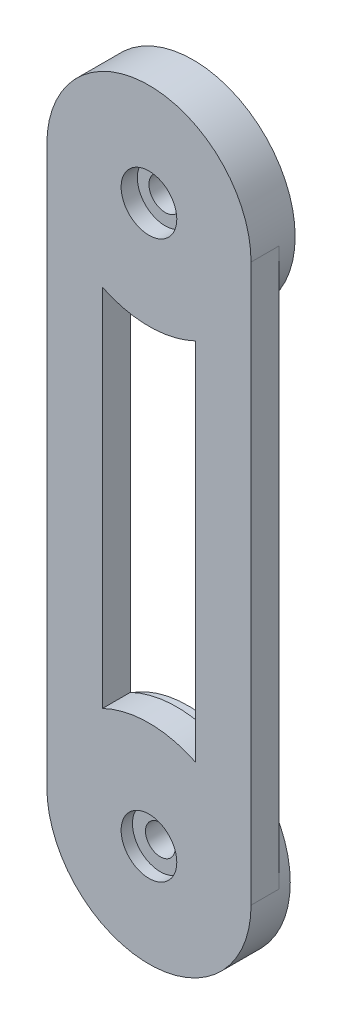
SolidWorks part; units mm, degrees
ref_plane "Front Plane" through (0, 0, 0) normal (0, 0, 1) x (1, 0, 0)
ref_plane "Top Plane" through (0, 0, 0) normal (0, 1, 0) x (1, 0, 0)
ref_plane "Right Plane" through (0, 0, 0) normal (1, 0, 0) x (0, 0, -1)
sketch "Sketch1" plane through (0, 0, 0) normal (0, 0, 1) x (1, 0, 0)
  line L0 (0, 30) -> (0, -30) construction
  line L1 (-11, 30) -> (-11, -30)
  line L2 (11, 30) -> (11, -30)
  line L5 (-5, 19.6438) -> (-5, -19.6438)
  line L7 (5, 19.6438) -> (5, -19.6438)
  circle A0 centre (0, 30) radius 11
  circle A1 centre (0, -30) radius 11
  circle A2 centre (0, 30) radius 11
  arc A3 (-5, 19.6438) -> (5, 19.6438) centre (0, 30) ccw
  arc A4 (5, -19.6438) -> (-5, -19.6438) centre (0, -30) ccw
  point P8 (0, 0)
  dimension "D2" = 22
  dimension "D3" = 23
  dimension "D1" = 60
  dimension "D4" = 6
  dimension "D5" = 6
extrude "Boss-Extrude1" add sketch "Sketch1" along normal blind 3 contours A0 | L0 A0 L1 A1 | A1 | A0 L0 A1 L2 region at (0, 18.9361, 0) region at (0, 30, 0) region at (0, -30, 0)
extrude "Boss-Extrude2" add sketch "Sketch1<3>" against normal blind 1.75 contours A0 region at (0, 30, 0)
sketch "Sketch1<3>" plane through (0, 0, 0) normal (0, 0, 1) x (1, 0, 0) same geometry as "Sketch1"
sketch "Sketch2" plane through (0, 0, 3) normal (0, 0, 1) x (1, 0, 0)
  circle A0 centre (0, 30) radius 1.75
  circle A3 centre (0, 30) radius 3
  dimension "D1" = 3.5
  dimension "D2" = 6
extrude "Cut-Extrude1" cut sketch "Sketch2" against normal up to surface (4.75 mm away) contours A0 region at (0, 30, 3) up to face at (11, 30, -1.75)
extrude "Cut-Extrude2" cut sketch "Sketch2<3>" against normal offset from surface (1.75 mm away) 3 contours A3 A0 region at (-2.9151, 30, 3) up to face at (1.75, 30, -1.75)
sketch "Sketch2<3>" plane through (0, 0, 3) normal (0, 0, 1) x (1, 0, 0) same geometry as "Sketch2"
extrude "Boss-Extrude3" add sketch "Sketch1<4>" against normal blind 1.225 contours A1 region at (0, -30, 0)
sketch "Sketch1<4>" plane through (0, 0, 0) normal (0, 0, 1) x (1, 0, 0) same geometry as "Sketch1"
sketch "Sketch3" plane through (0, 0, 3) normal (0, 0, 1) x (1, 0, 0)
  circle A0 centre (0, -30) radius 1.6
  circle A1 centre (0, -30) radius 3
  dimension "D1" = 3.2
  dimension "D2" = 6
extrude "Cut-Extrude3" cut sketch "Sketch3" against normal up to surface (4.225 mm away) contours A0 region at (0, -30, 3) up to face at (11, -30, -1.225)
extrude "Cut-Extrude4" cut sketch "Sketch3<3>" against normal offset from surface (1.225 mm away) 3 up to face at (1.6, -30, -1.225)
sketch "Sketch3<3>" plane through (0, 0, 3) normal (0, 0, 1) x (1, 0, 0) same geometry as "Sketch3"
